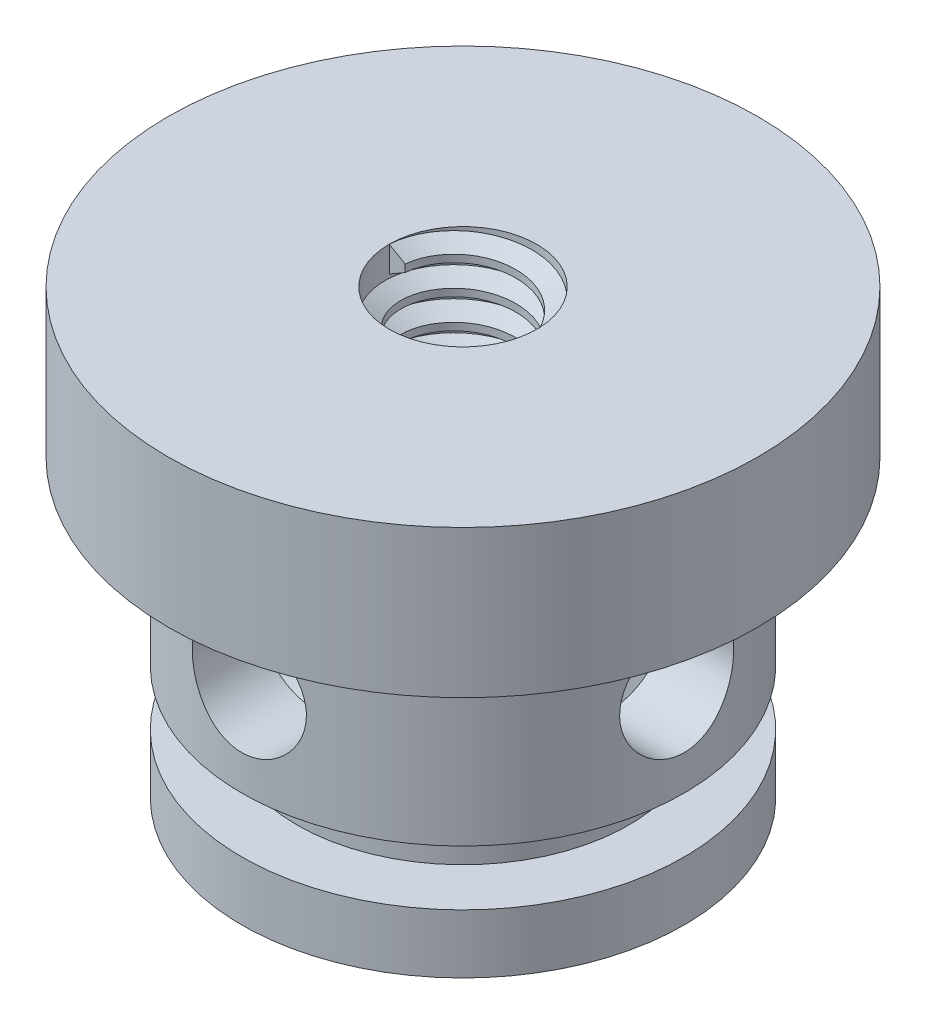
SolidWorks part; units mm, degrees
material "1060 Alloy"
ref_plane "Front Plane" through (0, 0, 0) normal (0, 0, 1) x (1, 0, 0)
ref_plane "Top Plane" through (0, 0, 0) normal (0, 1, 0) x (1, 0, 0)
ref_plane "Right Plane" through (0, 0, 0) normal (1, 0, 0) x (0, 0, -1)
sketch "Sketch2" plane through (0, 0, 0) normal (0, 0, 1) x (1, 0, 0)
  line L0 (0, 0) -> (-12.7, 0)
  line L1 (-12.7, 0) -> (-12.7, -6.35)
  line L2 (-12.7, -6.35) -> (-9.525, -6.35)
  line L3 (-9.525, -6.35) -> (-9.525, -19.05) construction
  line L4 (-9.525, -19.05) -> (0, -19.05)
  line L5 (0, -19.05) -> (0, 0)
  line L6 (-9.525, -19.05) -> (-9.525, -16.51)
  line L7 (-9.525, -16.51) -> (-7.1438, -16.51)
  line L8 (-7.1438, -16.51) -> (-7.1438, -14.1287)
  line L9 (-7.1438, -14.1287) -> (-9.525, -14.1287)
  line L10 (-9.525, -14.1287) -> (-9.525, -6.35)
  line L11 (-8.4931, -7.4978) -> (-8.4931, -12.2603) construction
  dimension "D1" = 12.7
  dimension "D2" = 6.35
  dimension "D3" = 12.7
  dimension "D4" = 9.525
  dimension "D5" = 2.3813
  dimension "D6" = 2.3813
  dimension "D7" = 2.54
  dimension "D8" = 4.7625
revolve "lathe_ops" add sketch "Sketch2" angle 360 about L5
sketch "hole_location" plane through (0, 0, 0) normal (0, 1, 0) x (1, 0, 0)
  circle A0 centre (0, 0) radius 3.175
  dimension "D1" = 6.35
extrude "Cut-Extrude1" cut sketch "hole_location" against normal blind 12.7 contours A0
thread "Thread1" pitch 1.27 method extrude profile "Thread Profile2" start angle 0, offset 0, length 10, pitch 1.27, diameter 6.35
ref_plane "Plane2" through (-3.175, 0, 0) normal (0, 0, 1) x (-1, 0, 0)
sketch "Thread Profile2" plane through (-3.175, 0, 0) normal (0, 0, 1) x (-1, 0, 0)
  line L0 (0, 0) -> (0, 1.27) construction
  line L11 (0, 0) -> (0, 1.1112)
  line L12 (0, 1.1112) -> (-0.6874, 0.7144)
  line L13 (-0.6874, 0.7144) -> (-0.6874, 0.3969)
  line L15 (-0.6874, 0.3969) -> (0, 0)
  line L17 (-0.6874, 0.5556) -> (0, 0.5556) construction
  point P2 (0, 0)
  dimension "Pitch" = 1.27
  dimension "Profile_Angle" = 60
  dimension "Profile_Land" = 0.3175
  dimension "Profile_Height" = 0.6874
ref_plane "Plane3" through (-9.525, 0, 0) normal (-1, 0, 0) x (0, 0, 1)
sketch "Sketch4" plane through (-9.525, 0, 0) normal (-1, 0, 0) x (0, 0, 1)
  line L0 (0, 0) -> (0, -10.16) construction
  line L3 (-9.525, -6.35) -> (9.525, -6.35) construction
  point P4 (0, -10.16)
  dimension "D1" = 3.81
hole_wizard "#10 (0.1935) Diameter Hole1" positions "Sketch4" profile "Sketch5" hole size "#10" standard "ANSI Inch"
sketch "Sketch5" plane through (-9.525, -10.16, 0) normal (0, 1, 0) x (0, 0, 1)
  line L0 (0, 0) -> (0, 4.6516)
  line L1 (0, 4.6516) -> (2.4574, 3.175)
  line L2 (2.4574, 3.175) -> (2.4574, 0)
  line L5 (2.4574, 0) -> (0, 0)
  line L10 (0, 4.6516) -> (-2.4574, 3.175) construction
  line L11 (0, -6.35) -> (0, 107.95) construction
  dimension "Hole Dia." = 4.9149
  dimension "Hole Depth" = 3.175
  dimension "Drill Angle" = 118
pattern_circular "CirPattern1" count 4 over 360 about axis through (0, -19.05, 0) along (0, -1, 0) of "#10 (0.1935) Diameter Hole1"
